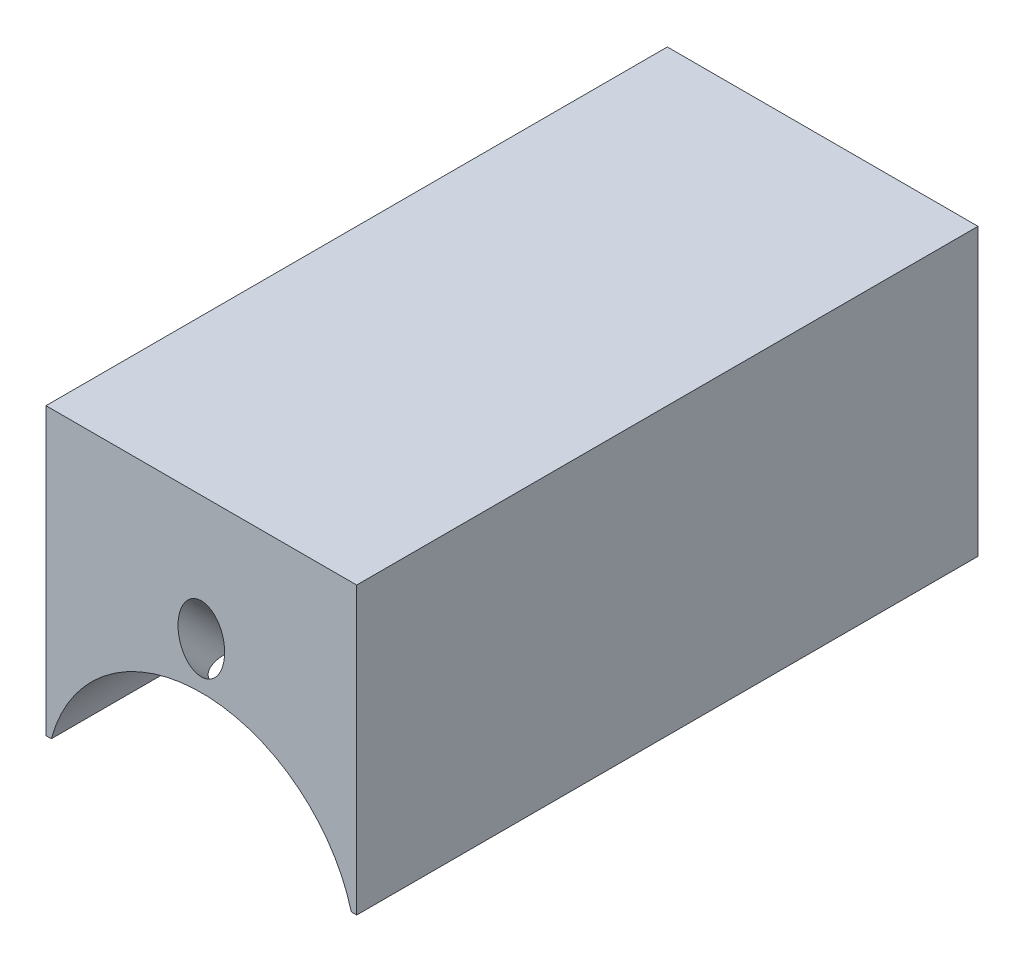
SolidWorks part; units mm, degrees
material "6061 Alloy"
ref_plane "Front Plane" through (0, 0, 0) normal (0, 0, 1) x (1, 0, 0)
ref_plane "Top Plane" through (0, 0, 0) normal (0, 1, 0) x (1, 0, 0)
ref_plane "Right Plane" through (0, 0, 0) normal (1, 0, 0) x (0, 0, -1)
sketch "Sketch2" plane through (0, 0, 0) normal (0, 0, 1) x (1, 0, 0)
  line L0 (0, 12.4473) -> (0, -8.5527)
  line L1 (-10, 12.4473) -> (10, 12.4473)
  line L2 (-10, 12.4473) -> (-10, -5.9527)
  line L3 (-10, -5.9527) -> (10, -5.9527)
  line L4 (10, 12.4473) -> (10, -5.9527)
  line L5 (0, 5.5944) -> (0, -2.8148)
  circle A0 centre (0, -8.5527) radius 10
  dimension "D1" = 20
  dimension "D2" = 18.4
  dimension "D3" = 21
extrude "Boss-Extrude1" add sketch "Sketch2" along normal blind 40 contours A0 L3 L4 L1 L0 | A0 L0 L1 L2 L3 region at (5.4416, 5.7126, 0) region at (-5.4416, 5.7126, 0)
sketch "Sketch5" plane through (0, 0, 0) normal (1, 0, 0) x (0, 0, -1)
  line L0 (-40, 12.4473) -> (-40, 4.4473)
  line L1 (-40, 12.4473) -> (-40, -5.9527) construction
  line L2 (-40, 4.4473) -> (-34.3431, 10.1042)
  line L3 (-34.3431, 10.1042) -> (-45.6569, -1.2095) construction
  circle A0 centre (-40, 4.4473) radius 8
  dimension "D1" = 8
ref_plane "Plane1" through (0, 22.2237, 22.2237) normal (0, 0.7071, 0.7071) x (0, -0.7071, 0.7071)
sketch "Sketch6" plane through (0, 22.2237, 22.2237) normal (0, 0.7071, 0.7071) x (0, -0.7071, 0.7071)
  circle A0 centre (25.1395, 0) radius 1.5
extrude "Cut-Extrude4" cut sketch "Sketch6" against normal through all both and the other way through all
sketch "Sketch8" plane through (0, 0, 0) normal (1, 0, 0) x (0, 0, -1)
  line L0 (0, 12.4473) -> (0, 4.4473)
  line L1 (0, 12.4473) -> (0, -5.9527) construction
  line L2 (0, 4.4473) -> (5.6569, -1.2095)
  line L3 (5.6569, -1.2095) -> (-5.6569, 10.1042) construction
  circle A0 centre (0, 4.4473) radius 8
  dimension "D1" = 8
ref_plane "Plane2" through (0, 2.2237, -2.2237) normal (0, 0.7071, -0.7071) x (0, 0.7071, 0.7071)
sketch "Sketch9" plane through (0, 2.2237, -2.2237) normal (0, 0.7071, -0.7071) x (0, 0.7071, 0.7071)
  circle A0 centre (3.1447, 0) radius 1.5
extrude "Cut-Extrude5" cut sketch "Sketch9" against normal through all both and the other way through all
sketch "Sketch10" plane through (0, 0, 0) normal (0, 1, 0) x (1, 0, 0)
  line L0 (-10, -40) -> (10, -40) construction
  circle A0 centre (0, -20) radius 1.5
  dimension "D1" = 20
sketch "Sketch13" plane through (0, 12.4473, 0) normal (0, 1, 0) x (1, 0, 0)
  circle A0 centre (0, -20) radius 1.5
sketch "Sketch14" plane through (0, 0, 0) normal (0, 0, 1) x (1, 0, 0)
  line L0 (0, 1.4473) -> (12.2087, 1.4473)
  arc A0 (9.6561, -5.9527) -> (-9.6561, -5.9527) centre (0, -8.5527) ccw construction
ref_plane "Plane4" through (0, 1.4473, 0) normal (0, -1, 0) x (1, 0, 0)
sketch "Sketch16" plane through (0, 1.4473, 0) normal (0, -1, 0) x (1, 0, 0)
  circle A0 centre (0, 20) radius 1.5
extrude "Cut-Extrude8" cut sketch "Sketch16" against normal blind 2.5 and the other way blind 10
